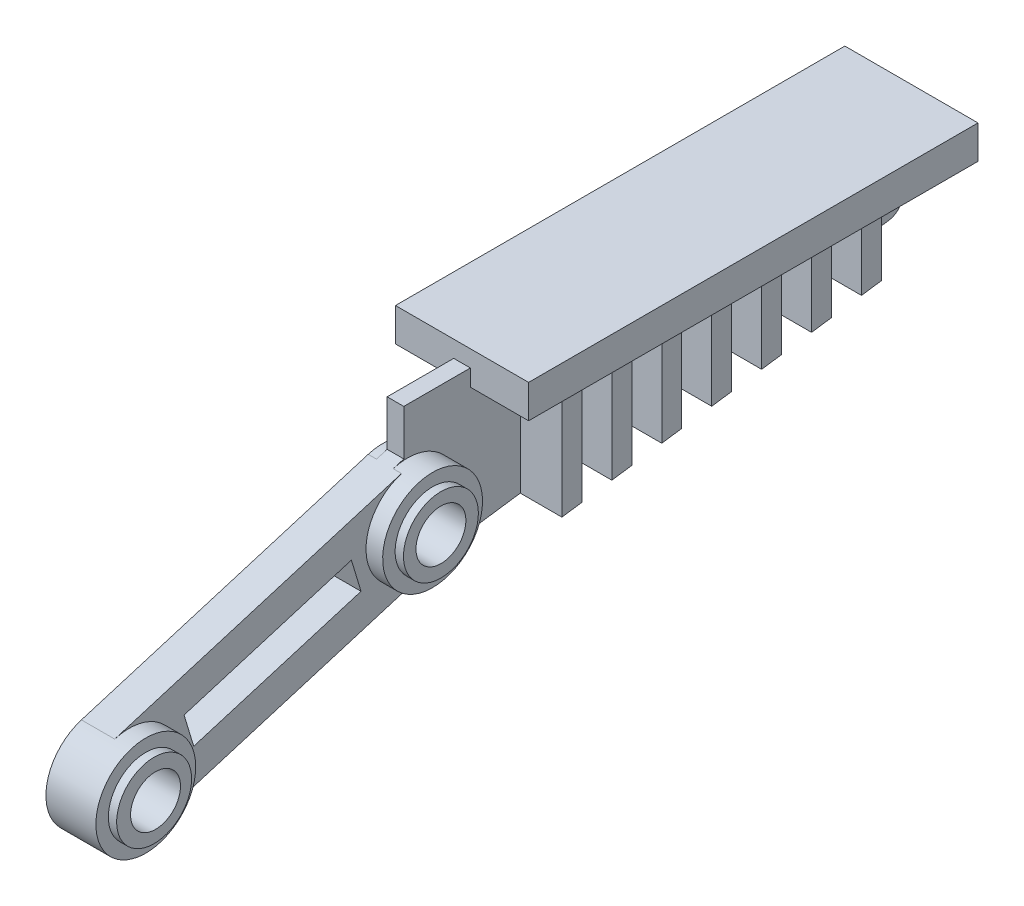
SolidWorks part; units mm, degrees
note: '?' marks a value the reader was unsure of.
material "ABS"
ref_plane "Front Plane" through (0, 0, 0) normal (0, 0, 1) x (1, 0, 0)
ref_plane "Top Plane" through (0, 0, 0) normal (0, 1, 0) x (1, 0, 0)
ref_plane "Right Plane" through (0, 0, 0) normal (1, 0, 0) x (0, 0, -1)
sketch "Sketch1" plane through (0, 0, 0) normal (0, 1, 0) x (1, 0, 0)
  line L1 (-4, 13.5) -> (4, 13.5)
  line L2 (-4, 13.5) -> (-4, -13.5)
  line L3 (-4, -13.5) -> (4, -13.5)
  line L4 (4, 13.5) -> (4, -13.5)
  line L5 (-4, 13.5) -> (4, -13.5) construction
  line L6 (-4, -13.5) -> (4, 13.5) construction
  point P0 (0, 0)
  dimension "D1" = 8
  dimension "D2" = 27
extrude "Boss-Extrude1" add sketch "Sketch1" against normal blind 2
sketch "Sketch4" plane through (0, 0, 0) normal (1, 0, 0) x (0, 0, -1)
  line L0 (13.5, 0) -> (13.5, -2)
  line L1 (13.5, -2) -> (12.2639, -5.8042)
  line L2 (12.2639, -5.8042) -> (-17.5, -10)
  line L3 (13.5, -2) -> (-13.5, -2) construction
  line L4 (13.5, 0) -> (-13.5, 0)
  line L5 (4.4, 0) -> (-4.4, 0) construction
  line L6 (-13.5, 0) -> (-13.5, -1)
  line L7 (-13.5, -1) -> (-17.5, -1)
  line L8 (-17.5, -10) -> (-19.2346, -4.2562) construction
  line L9 (-17.5, -1) -> (-17.5, -10) construction
  line L10 (-17.5, -10) -> (-33.6327, -14.8719)
  line L11 (-19.2346, -4.2562) -> (-35.3673, -9.1281)
  line L12 (-19.2346, -4.2562) -> (-17.5012, -3.7327)
  line L13 (-17.5012, -3.7327) -> (-17.5, -1)
  line L14 (-34.5, -12) -> (-17.2686, -6.7963) construction
  arc A0 (-35.3673, -9.1281) -> (-33.6327, -14.8719) centre (-34.5, -12) ccw
  dimension "D9" = 6
  dimension "D11" = 15
  dimension "D1" = 13.5
  dimension "D2" = 2
  dimension "D3" = 4
  dimension "D4" = 72
  dimension "D5" = 27
  dimension "D6" = 1
  dimension "D7" = 4
  dimension "D8" = 90
  dimension "D10" = 51
  dimension "D12" = 9
  dimension "D13" = 6
  dimension "D14" = 2.7327
  dimension "D15" = 18
extrude "Boss-Extrude2" add sketch "Sketch4" along normal mid plane 1
sketch "Sketch5" plane through (-0.5, 0, 0) normal (-1, 0, 0) x (0, 0, 1)
  line L0 (17.5012, -3.7327) -> (35.3673, -9.1281) construction
  line L1 (33.6327, -14.8719) -> (16.4223, -9.6745)
  line L2 (35.3673, -9.1281) -> (18.1359, -3.9244)
  arc A0 (33.6327, -14.8719) -> (35.3673, -9.1281) centre (34.5, -12) ccw
  arc A1 (18.1359, -3.9244) -> (16.4223, -9.6745) centre (17.2686, -6.7963) ccw
  arc M8 (33.6327, -14.8719) -> (35.3673, -9.1281) centre (34.5, -12) ccw
  line M9 (35.3673, -9.1281) -> (17.5012, -3.7327)
  dimension "D2" = 6
  dimension "D3" = 0
  dimension "D4" = 18
extrude "Boss-Extrude3" add sketch "Sketch5" along normal blind 0.5 contours A1 L1 M9 M8
sketch "Sketch6" plane through (0.5, 0, 0) normal (1, 0, 0) x (0, 0, -1)
  line L0 (-17.5012, -3.7327) -> (-35.3673, -9.1281) construction
  line L1 (-35.3673, -9.1281) -> (-18.1359, -3.9244)
  line L2 (-33.6327, -14.8719) -> (-16.4013, -9.6682)
  arc A1 (-35.3673, -9.1281) -> (-33.6327, -14.8719) centre (-34.5, -12) ccw
  arc A2 (-16.4013, -9.6682) -> (-18.1359, -3.9244) centre (-17.2686, -6.7963) ccw
  dimension "D1" = 6
  dimension "D4" = 3
  dimension "D3" = 18
extrude "Boss-Extrude4" add sketch "Sketch6" along normal blind 0.5
sketch "Sketch7" plane through (-1, 0, 0) normal (-1, 0, 0) x (0, 0, 1)
  circle A0 centre (17.2686, -6.7963) radius 2.25
  dimension "D1" = 4.5
extrude "Boss-Extrude5" add sketch "Sketch7" along normal blind 0.5
sketch "Sketch8" plane through (1, 0, 0) normal (1, 0, 0) x (0, 0, -1)
  circle A0 centre (-34.5, -12) radius 3
  circle A1 centre (-17.2686, -6.7963) radius 3
  arc A2 (-16.4013, -9.6682) -> (-18.1359, -3.9244) centre (-17.2686, -6.7963) ccw construction
  dimension "D1" = 6
  dimension "D2" = 0
extrude "Boss-Extrude6" add sketch "Sketch8" along normal blind 1
sketch "Sketch9" plane through (2, 0, 0) normal (1, 0, 0) x (0, 0, -1)
  circle A0 centre (-34.5, -12) radius 2.25
  circle A1 centre (-17.2686, -6.7963) radius 2.25
  dimension "D1" = 4.5
  dimension "D2" = 4.5
extrude "Boss-Extrude7" add sketch "Sketch9" along normal blind 0.5
sketch "Sketch10" plane through (2.5, 0, 0) normal (1, 0, 0) x (0, 0, -1)
  circle A0 centre (-17.2686, -6.7963) radius 1.5
  circle A1 centre (-34.4157, -12.0513) radius 1.5
  dimension "D1" = 3
  dimension "D2" = 3
extrude "Cut-Extrude1" cut sketch "Sketch10" against normal through all
ref_axis "Axis2" through (1, -14.8719, 33.6327) along (0, 0.2891, -0.9573)?
ref_plane "Plane1" through (1, 0, 0) normal (-1, 0, 0) x (0, 0.2891, -0.9573)
sketch "Sketch14" plane through (1, 0, 0) normal (-1, 0, 0) x (0, 0.2891, -0.9573)
  line L0 (-18.496, -1.4861) -> (-36.496, -1.4861) construction
  line L1 (-22.246, 2.5139) -> (-32.746, 2.5139)
  line L2 (-22.246, 2.5139) -> (-22.246, 0.5139)
  line L3 (-22.246, 0.5139) -> (-32.746, 0.5139)
  line L4 (-32.746, 2.5139) -> (-32.746, 0.5139)
  line L5 (-22.246, 2.5139) -> (-32.746, 0.5139) construction
  line L6 (-22.246, 0.5139) -> (-32.746, 2.5139) construction
  point P0 (-27.496, 1.5139)
  dimension "D1" = 3
  dimension "D2" = 2
  dimension "D3" = 10.5
  dimension "D4" = 9
extrude "Cut-Extrude2" cut sketch "Sketch14" along normal blind 1.8
fillet "Fillet1" radius 1 1 edges at (0, -5.8042, -12.2639)
ref_axis "Axis3" through (-1, -14.8719, 33.6327) along (0, 0.2891, -0.9573)?
ref_plane "Plane2" through (-1, 0, 0) normal (1, 0, 0) x (0, 0.2891, -0.9573)
sketch "Sketch15" plane through (-1, 0, 0) normal (1, 0, 0) x (0, 0.2891, -0.9573)
  line L0 (-36.496, 1.4863) -> (-18.496, 1.4862) construction
  line L1 (-25.496, 0.2363) -> (-29.496, 0.2363)
  line L2 (-25.496, 0.2363) -> (-25.496, -3.2637)
  line L3 (-25.496, -3.2637) -> (-29.496, -3.2637)
  line L4 (-29.496, 0.2363) -> (-29.496, -3.2637)
  line L5 (-25.496, 0.2363) -> (-29.496, -3.2637) construction
  line L6 (-25.496, -3.2637) -> (-29.496, 0.2363) construction
  arc A0 (-36.496, 1.4863) -> (-36.496, -4.5137) centre (-36.496, -1.5137) ccw construction
  point P0 (-27.496, -1.5137)
  dimension "D1" = 3
  dimension "D2" = 3.5
  dimension "D3" = 4
  dimension "D4" = 9
extrude "Cut-Extrude5" cut sketch "Sketch15" along normal blind 0.1
sketch "Sketch19" plane through (0, -2, 0) normal (0, -1, 0) x (1, 0, 0)
  line L0 (0, -8.25) -> (0, 8.25) construction
  line L1 (-3, 9.3) -> (3, 9.3)
  line L2 (-3, 9.3) -> (-3, 10.5)
  line L3 (-3, 10.5) -> (3, 10.5)
  line L4 (3, 9.3) -> (3, 10.5)
  line L5 (-3, 9.3) -> (3, 10.5) construction
  line L6 (-3, 10.5) -> (3, 9.3) construction
  line L7 (-4, 13.5) -> (-0.5, 13.5) construction
  point P0 (0, 9.9)
  dimension "D1" = 6
  dimension "D2" = 1.2
  dimension "D3" = 3
extrude "Boss-Extrude8" add sketch "Sketch19" along normal blind 7.1
pattern_linear "LPattern1" count 7 spacing 3 along (0, 0, -1) of "Boss-Extrude8"
ref_axis "Axis4" through (0.5, -7.5753, 0.3) along (0, 0.1396, -0.9902)?
ref_plane "Plane3" through (0.5, 0, 0) normal (-1, 0, 0) x (0, 0.1396, -0.9902)
sketch "Sketch20" plane through (0.5, 0, 0) normal (-1, 0, 0) x (0, 0.1396, -0.9902)
  line L1 (7.7345, 7.4593) -> (-12.2449, 7.4593)
  line L2 (7.7345, 7.4593) -> (7.7345, 10.8806)
  line L3 (7.7345, 10.8806) -> (-12.2449, 10.8806)
  line L4 (-12.2449, 7.4593) -> (-12.2449, 10.8806)
extrude "Cut-Extrude6" cut sketch "Sketch20" against normal mid plane 7.1
sketch "Sketch21" plane through (1, 0, 0) normal (1, 0, 0) x (0, 0, -1)
  point P0 (-17.2686, -6.7963)
  point P1 (5.7314, 14.2037)
  dimension "D1" = 21
  dimension "D2" = 23
ref_plane "RH_GripPanel" through (0, 4.8923, 4.4668) normal (0, 0.7385, 0.6743) x (1, 0, 0)
equation "\"D2@Sketch9\"=\"D1@Sketch9\""
equation "\"D2@Sketch10\"=\"D1@Sketch10\""
